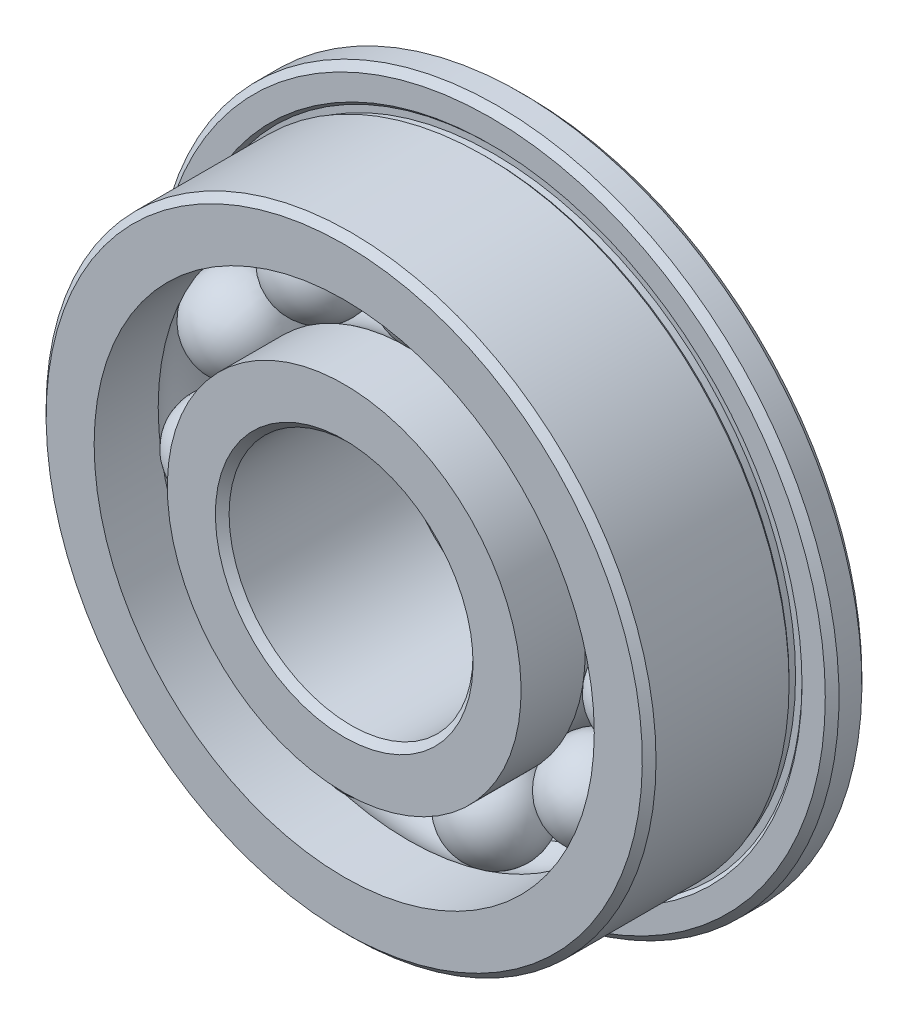
SolidWorks part; units mm, degrees
ref_plane "Front Plane" through (0, 0, 0) normal (0, 0, 1) x (1, 0, 0)
ref_plane "Top Plane" through (0, 0, 0) normal (0, 1, 0) x (1, 0, 0)
ref_plane "Right Plane" through (0, 0, 0) normal (1, 0, 0) x (0, 0, -1)
sketch "Sketch1" plane through (0, 0, 0) normal (1, 0, 0) x (0, 0, -1)
  line L0 (0, 5) -> (0, -5) construction
  line L1 (-1.5, 5) -> (1.5, 5) construction
  line L2 (0, 0) -> (1.5, 0) construction
  line L3 (1.5, 5.6) -> (1.5, -5.6) construction
  line L4 (1.5, -5.6) -> (0.9, -5.6) construction
  line L5 (1.5, 2) -> (0, 2) construction
  line L6 (1.5, 2) -> (1.5, -2) construction
  dimension "OD" = 10
  dimension "Width" = 3
  dimension "Flange Thickness" = 0.6
  dimension "ID" = 4
  dimension "Flange OD" = 11.2
sketch "Sketch2" plane through (0, 0, 0) normal (1, 0, 0) x (0, 0, -1)
  line L0 (1.5, 5.6) -> (0.9, 5.6)
  line L1 (0.9, 5.6) -> (0.9, 5.1061)
  line L2 (0.7939, 5) -> (-1.5, 5)
  line L3 (-1.5, 5) -> (-1.5, 4.1)
  line L4 (-1.5, 4.1) -> (-0.45, 4.1)
  line L5 (1.5, 5.6) -> (1.5, -5.6) construction
  line L6 (1.5, 4.1) -> (1.5, 5.6)
  line L7 (1.5, 2) -> (-1.5, 2)
  line L8 (-1.5, 2) -> (-1.5, 2.9)
  line L9 (-1.5, 2.9) -> (-0.45, 2.9)
  line L10 (1.5, 2.9) -> (1.5, 2)
  line L11 (0, 5) -> (0, 2) construction
  line L12 (-0.75, 3.5) -> (0.75, 3.5) construction
  line L13 (0.45, 4.1) -> (1.5, 4.1)
  line L14 (0.45, 2.9) -> (1.5, 2.9)
  line L15 (0.9, 5.1061) -> (0.953, 5.053)
  line L16 (0.953, 5.053) -> (0.953, 4.947)
  line L17 (0.953, 4.947) -> (0.847, 4.947)
  line L18 (0.847, 4.947) -> (0.7939, 5)
  line L19 (0.9, 5) -> (0.953, 4.947) construction
  line L20 (0.953, 5.053) -> (0.847, 4.947) construction
  line L21 (0.7939, 5) -> (0.9, 5) construction
  line L22 (0.9, 5) -> (0.9, 5.1061) construction
  circle A0 centre (0, 3.5) radius 0.75 construction
  arc A1 (-0.45, 4.1) -> (0.45, 4.1) centre (0, 3.5) cw
  arc A2 (-0.45, 2.9) -> (0.45, 2.9) centre (0, 3.5) ccw
  dimension "D1" = 3
  dimension "Ball Dia." = 1.5
  dimension "D2" = 135
  dimension "D3" = 0.15
  dimension "D4" = 1.2
  dimension "Race Thikness" = 0.9
revolve "Revolve1" add sketch "Sketch2" angle 360 about L2
fillet "Fillet1" radius 0.1125 3 edges at (0, -5.6, -1.5) (0, -5.6, -0.9) (0, -5, 1.5) profile chamfer
sketch "Sketch3" plane through (0, 0, 0) normal (0, 0, 1) x (1, 0, 0)
  line L0 (-2, 0) -> (2, 0) construction
  line L1 (-5, 0) -> (5, 0) construction
  point P5 (0, 0)
  dimension "ID2" = 4
  dimension "OD2" = 10
fillet "Fillet2" radius 0.1125 2 edges at (0, -2, -1.5) (0, -2, 1.5) profile chamfer
sketch "Sketch7" plane through (0, 0, 0) normal (0, 0, 1) x (1, 0, 0)
  line L0 (0, 4.25) -> (0, 2.75)
  line L1 (0, 5.6) -> (0, -5.6) construction
  line L2 (-0.9324, 4.25) -> (0, 0) construction
  line L3 (0, 0) -> (0.9324, 4.25) construction
  line L4 (0.9324, 4.25) -> (-0.9324, 4.25) construction
  circle A0 centre (0, 3.5) radius 0.75 construction
  circle A1 centre (0, 0) radius 4.25 construction
  circle A2 centre (0, 0) radius 2.75 construction
  arc A4 (0, 4.25) -> (0, 2.75) centre (0, 3.5) ccw
  dimension "D1" = 24.747
revolve "Revolve3" add sketch "Sketch7" angle 360 about L0
pattern_circular "CirPattern3" count 11 over 360 about axis through (0, 0, 0) along (0, 0, -1) of bodies 107
sketch "Sketch8" plane through (0, 0, 0) normal (1, 0, 0) x (0, 0, -1)
  line L0 (-1.5, 5) -> (1.5, 5) construction
  line L1 (1.5, 5) -> (1.5, 5.6) construction
  line L2 (-1.5, -5) -> (1.5, -5) construction
  line L3 (1.5, 5.6) -> (1.5, -5.6) construction
  dimension "D1" = 10
equation "\"Ball Dia.@Sketch2\" = ( \"OD@Sketch1\" - \"ID@Sketch1\" ) * .25"
equation "\"D3@Sketch2\"=\"Flange Thickness@Sketch1\"/4"
equation "\"D1@Fillet1\" = \"Race Thikness@Sketch2\" / 8"
equation "\"ID2@Sketch3\" = \"ID@Sketch1\""
equation "\"OD2@Sketch3\" = \"OD@Sketch1\""
equation "\"D1@Fillet2\" = \"Race Thikness@Sketch2\" / 8"
equation "\"D1@CirPattern3\"=360/\"D1@Sketch7\"-4"
equation "\"D4@Sketch2\" = ( \"OD@Sketch1\" - \"ID@Sketch1\" ) * .2"
